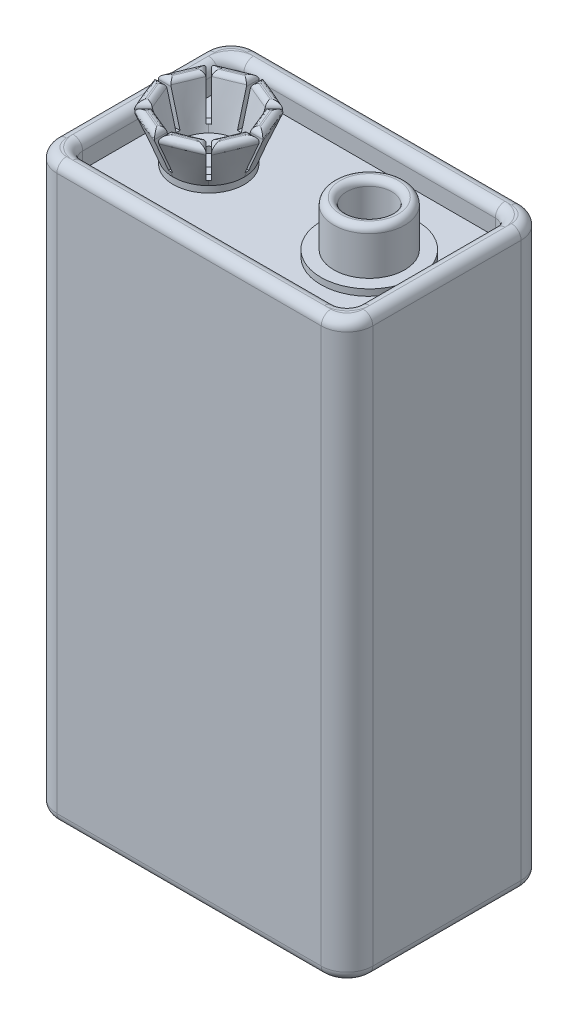
SolidWorks part; units mm, degrees
ref_plane "Front Plane" through (0, 0, 0) normal (0, 0, 1) x (1, 0, 0)
ref_plane "Top Plane" through (0, 0, 0) normal (0, 1, 0) x (1, 0, 0)
ref_plane "Right Plane" through (0, 0, 0) normal (1, 0, 0) x (0, 0, -1)
sketch "Sketch1" plane through (0, 0, 0) normal (0, 1, 0) x (1, 0, 0)
  line L1 (-10.25, -7.75) -> (10.25, -7.75)
  line L2 (-12.25, -5.75) -> (-12.25, 5.75)
  line L3 (-10.25, 7.75) -> (10.25, 7.75)
  line L4 (12.25, -5.75) -> (12.25, 5.75)
  line L5 (-12.25, -7.75) -> (12.25, 7.75) construction
  line L6 (-12.25, 7.75) -> (12.25, -7.75) construction
  arc A0 (10.25, -7.75) -> (12.25, -5.75) centre (10.25, -5.75) ccw
  arc A1 (-10.25, -7.75) -> (-12.25, -5.75) centre (-10.25, -5.75) cw
  arc A2 (10.25, 7.75) -> (12.25, 5.75) centre (10.25, 5.75) cw
  arc A3 (-12.25, 5.75) -> (-10.25, 7.75) centre (-10.25, 5.75) cw
  point P0 (0, 0)
  dimension "D3" = 2
  dimension "D1" = 24.5
  dimension "D2" = 15.5
extrude "Boss-Extrude1" add sketch "Sketch1" along normal blind 44.5
sketch "Sketch2" plane through (0, 0, 0) normal (0, -1, 0) x (-1, 0, 0)
  line L0 (10.25, -7.75) -> (-10.25, -7.75) construction
  line L1 (9.25, 6.25) -> (-9.25, 6.25)
  line L2 (10.75, 4.75) -> (10.75, -4.75)
  line L3 (9.25, -6.25) -> (-9.25, -6.25)
  line L4 (-10.75, 4.75) -> (-10.75, -4.75)
  line L5 (10.75, 6.25) -> (-10.75, -6.25) construction
  line L6 (10.75, -6.25) -> (-10.75, 6.25) construction
  line L7 (-12.25, -5.75) -> (-12.25, 5.75) construction
  arc A0 (-9.25, 6.25) -> (-10.75, 4.75) centre (-9.25, 4.75) ccw
  arc A1 (9.25, 6.25) -> (10.75, 4.75) centre (9.25, 4.75) cw
  arc A2 (-9.25, -6.25) -> (-10.75, -4.75) centre (-9.25, -4.75) cw
  arc A3 (10.75, -4.75) -> (9.25, -6.25) centre (9.25, -4.75) cw
  point P0 (0, 0)
  dimension "D3" = 1.5
  dimension "D1" = 1.5
  dimension "D2" = 1.5
extrude "Cut-Extrude1" cut sketch "Sketch2" against normal blind 2
fillet "Fillet1" radius 0.75 16 edges at (12.25, 0, 0) (11.6642, 0, -7.1642) (0, 0, -7.75) (-11.6642, 0, -7.1642) (-12.25, 0, 0) (-11.6642, 0, 7.1642) (0, 0, 7.75) (11.6642, 0, 7.1642) (10.3107, 0, 5.8107) (0, 0, 6.25) (-10.3107, 0, 5.8107) (-10.75, 0, 0) (-10.3107, 0, -5.8107) (0, 0, -6.25) (10.3107, 0, -5.8107) (10.75, 0, 0)
sketch "Sketch3" plane through (0, 2, 0) normal (0, -1, 0) x (-1, 0, 0)
  line L1 (9, 5.5) -> (-9, 5.5)
  line L2 (10, 4.5) -> (10, -4.5)
  line L3 (9, -5.5) -> (-9, -5.5)
  line L4 (-10, 4.5) -> (-10, -4.5)
  line L5 (10, 5.5) -> (-10, -5.5) construction
  line L6 (10, -5.5) -> (-10, 5.5) construction
  arc A0 (-9, 5.5) -> (-10, 4.5) centre (-9, 4.5) ccw
  arc A1 (9, 5.5) -> (10, 4.5) centre (9, 4.5) cw
  arc A2 (-9, -5.5) -> (-10, -4.5) centre (-9, -4.5) cw
  arc A3 (10, -4.5) -> (9, -5.5) centre (9, -4.5) cw
  point P0 (0, 0)
  dimension "D3" = 1
  dimension "D1" = 20
  dimension "D2" = 11
extrude "Boss-Extrude2" add sketch "Sketch3" along normal blind 1
fillet "Fillet2" radius 0.5 16 edges at (0, 1, -5.5) (-9.7071, 1, -5.2071) (-10, 1, 0) (-9.7071, 1, 5.2071) (0, 1, 5.5) (9.7071, 1, 5.2071) (10, 1, 0) (9.7071, 1, -5.2071) (-10, 2, 0) (-9.7071, 2, 5.2071) (0, 2, 5.5) (9.7071, 2, 5.2071) (10, 2, 0) (9.7071, 2, -5.2071) (0, 2, -5.5) (-9.7071, 2, -5.2071)
sketch "Sketch4" plane through (0, 44.5, 0) normal (0, 1, 0) x (1, 0, 0)
  line L1 (10.25, 7.75) -> (-10.25, 7.75) construction
  line L2 (-9.75, -6.25) -> (9.75, -6.25)
  line L3 (-10.75, -5.25) -> (-10.75, 5.25)
  line L4 (-9.75, 6.25) -> (9.75, 6.25)
  line L5 (10.75, -5.25) -> (10.75, 5.25)
  line L6 (-10.75, -6.25) -> (10.75, 6.25) construction
  line L8 (-10.75, 6.25) -> (10.75, -6.25) construction
  line L9 (12.25, -5.75) -> (12.25, 5.75) construction
  arc A0 (9.75, -6.25) -> (10.75, -5.25) centre (9.75, -5.25) ccw
  arc A1 (-9.75, -6.25) -> (-10.75, -5.25) centre (-9.75, -5.25) cw
  arc A2 (9.75, 6.25) -> (10.75, 5.25) centre (9.75, 5.25) cw
  arc A3 (-10.75, 5.25) -> (-9.75, 6.25) centre (-9.75, 5.25) cw
  point P0 (0, 0)
  dimension "D3" = 1
  dimension "D1" = 1.5
  dimension "D2" = 1.5
extrude "Cut-Extrude2" cut sketch "Sketch4" against normal blind 2
fillet "Fillet4" radius 0.75 16 edges at (0, 44.5, 7.75) (-11.6642, 44.5, 7.1642) (-12.25, 44.5, 0) (-11.6642, 44.5, -7.1642) (0, 44.5, -7.75) (11.6642, 44.5, -7.1642) (12.25, 44.5, 0) (11.6642, 44.5, 7.1642) (10.75, 44.5, 0) (10.4571, 44.5, -5.9571) (0, 44.5, -6.25) (-10.4571, 44.5, -5.9571) (-10.75, 44.5, 0) (-10.4571, 44.5, 5.9571) (0, 44.5, 6.25) (10.4571, 44.5, 5.9571)
sketch "Sketch5" plane through (0, 42.5, 0) normal (0, 1, 0) x (1, 0, 0)
  circle A1 centre (6.225, 0) radius 3.75
extrude "Boss-Extrude3" add sketch "Sketch5" along normal blind 0.5
sketch "Sketch6" plane through (0, 43, 0) normal (0, 1, 0) x (1, 0, 0)
  circle A0 centre (6.225, 0) radius 2.75
  circle A1 centre (6.225, 0) radius 1.75
  dimension "D1" = 5.5
  dimension "D4" = 3.5
  dimension "D2" = 6.225
  dimension "D3" = 0
extrude "Boss-Extrude4" add sketch "Sketch6" along normal blind 3.5
sketch "Sketch7" plane through (0, 43, 0) normal (0, 1, 0) x (1, 0, 0)
  circle A0 centre (6.225, 0) radius 1
  dimension "D1" = 6.225
  dimension "D3" = 2
  dimension "D2" = 0
extrude "Cut-Extrude3" cut sketch "Sketch7" against normal blind 0.5
fillet "Fillet6" radius 0.5 2 edges at (6.225, 46.5, 1.75) (6.225, 46.5, 2.75)
sketch "Sketch8" plane through (0, 42.5, 0) normal (0, 1, 0) x (1, 0, 0)
  circle A0 centre (-6.225, 0) radius 2.75
  dimension "D1" = 5.5
  dimension "D2" = 6.225
  dimension "D3" = 0
extrude "Boss-Extrude5" add sketch "Sketch8" along normal blind 0.5
ref_plane "Plane1" through (0, 46.5, 0) normal (0, 1, 0) x (1, 0, 0)
sketch "Sketch9" plane through (0, 46.5, 0) normal (0, 1, 0) x (1, 0, 0)
  line L1 (-3.1523, 3.0502) -> (-6.209, 4.3295)
  line L2 (-6.209, 4.3295) -> (-9.2752, 3.0727)
  line L3 (-9.2752, 3.0727) -> (-10.5545, 0.016)
  line L4 (-10.5545, 0.016) -> (-9.2977, -3.0502)
  line L5 (-9.2977, -3.0502) -> (-6.241, -4.3295)
  line L6 (-6.241, -4.3295) -> (-3.1748, -3.0727)
  line L7 (-3.1748, -3.0727) -> (-1.8955, -0.016)
  line L8 (-1.8955, -0.016) -> (-3.1523, 3.0502)
  circle A0 centre (-6.225, 0) radius 4 construction
  dimension "D1" = 8
  dimension "D2" = 6.225
sketch "Sketch11" plane through (0, 43, 0) normal (0, 1, 0) x (1, 0, 0)
  circle A0 centre (-6.225, 0) radius 2.75
  dimension "D1" = 5.5
  dimension "D2" = 6.225
  dimension "D3" = 0
loft "Loft1" add profiles "Sketch11", "Sketch9" connector at (-7.1403, 43, 2.5932) connector at (-9.2977, 46.5, 3.0502)
sketch "Sketch12" plane through (0, 43, 0) normal (0, 1, 0) x (1, 0, 0)
  circle A0 centre (-6.225, 0) radius 2.25
  dimension "D1" = 4.5
sketch "Sketch14" plane through (0, 46.5, 0) normal (0, 1, 0) x (1, 0, 0)
  line L1 (-2.9778, 0) -> (-3.9289, 2.2961)
  line L2 (-3.9289, 2.2961) -> (-6.225, 3.2472)
  line L3 (-6.225, 3.2472) -> (-8.5211, 2.2961)
  line L4 (-8.5211, 2.2961) -> (-9.4722, 0)
  line L5 (-9.4722, 0) -> (-8.5211, -2.2961)
  line L6 (-8.5211, -2.2961) -> (-6.225, -3.2472)
  line L7 (-6.225, -3.2472) -> (-3.9289, -2.2961)
  line L8 (-3.9289, -2.2961) -> (-2.9778, 0)
  circle A0 centre (-6.225, 0) radius 3 construction
  dimension "D1" = 6
loft "Cut-Loft1" cut profiles "Sketch12", "Sketch14" connector at (-6.225, 43, 2.25) connector at (-6.225, 46.5, 3.2472)
sketch "Sketch16" plane through (0, 46.5, 0) normal (0, 1, 0) x (1, 0, 0)
  line L2 (-6.375, -4.5) -> (-6.075, -4.5)
  line L3 (-6.375, -4.5) -> (-6.375, 4.5)
  line L5 (-6.375, 4.5) -> (-6.075, 4.5)
  line L6 (-6.075, -4.5) -> (-6.075, 4.5)
  line L8 (-6.375, -4.5) -> (-6.075, 4.5) construction
  line L10 (-6.375, 4.5) -> (-6.075, -4.5) construction
  point P0 (-6.225, 0)
  dimension "D1" = 0.3
  dimension "D2" = 6.225
  dimension "D3" = 9
extrude "Cut-Extrude4" cut sketch "Sketch16" against normal blind 3
ref_axis "Axis1" through (-6.225, 43.1562, 0) along (0, -1, 0)
pattern_circular "CirPattern1" count 8 over 360 about axis through (-6.225, 43.1562, 0) along (0, -1, 0) of "Cut-Extrude4"
fillet "Fillet7" radius 0.4 32 edges
sketch "Sketch19" plane through (0, 43, 0) normal (0, 1, 0) x (1, 0, 0)
  circle A0 centre (-6.225, 0) radius 1
  dimension "D1" = 2
extrude "Cut-Extrude5" cut sketch "Sketch19" against normal blind 0.5 contours A0
